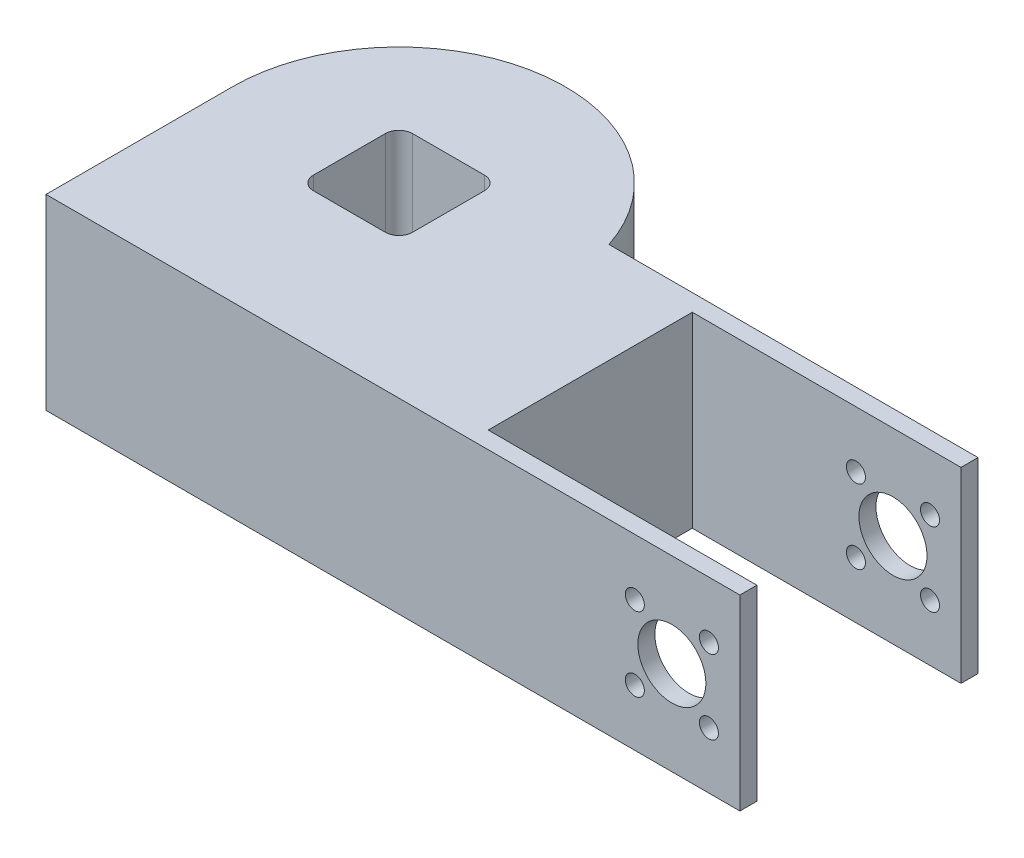
SolidWorks part; units mm, degrees
ref_plane "Front Plane" through (0, 0, 0) normal (0, 0, 1) x (1, 0, 0)
ref_plane "Top Plane" through (0, 0, 0) normal (0, 1, 0) x (1, 0, 0)
ref_plane "Right Plane" through (0, 0, 0) normal (1, 0, 0) x (0, 0, -1)
sketch "Sketch1" plane through (0, 0, 0) normal (0, 1, 0) x (1, 0, 0)
  circle A0 centre (0, 0) radius 31.0896
  dimension "D1" = 62.1792
extrude "Boss-Extrude1" add sketch "Sketch1" along normal blind 34.925
sketch "Sketch2" plane through (0, 34.925, 0) normal (0, 1, 0) x (1, 0, 0)
  line L0 (0, 0) -> (-31.0896, 0) construction
  line L1 (0, 0) -> (29.5534, 9.652) construction
  line L2 (-31.0896, 0) -> (-31.0896, -34.798)
  line L4 (45.1104, -34.798) -> (45.1104, 9.652)
  line L5 (-31.0896, -34.798) -> (45.1104, -34.798)
  line L7 (29.5534, 9.652) -> (45.1104, 9.652)
  circle A0 centre (0, 0) radius 31.0896 construction
  circle A2 centre (0, 0) radius 31.0896
  arc A3 (-31.0896, 0) -> (29.5534, 9.652) centre (0, 0) ccw
  dimension "D1" = 44.45
  dimension "D2" = 15.557
  dimension "D3" = 76.2
  dimension "D4" = 0
extrude "Boss-Extrude2" add sketch "Sketch2" against normal up to surface (34.925 mm away) up to face at (0, 0, 31.0896)
sketch "Sketch3" plane through (0, 34.925, 0) normal (0, 1, 0) x (1, 0, 0)
  line L0 (45.1104, -4.714) -> (45.1104, -34.798)
  line L2 (45.1104, -34.798) -> (98.4504, -34.798)
  line L3 (98.4504, -34.798) -> (98.4504, -31.623)
  line L4 (98.4504, -31.623) -> (48.2854, -31.623)
  line L5 (48.2854, -31.623) -> (48.2854, 6.477)
  line L6 (48.2854, 6.477) -> (98.4504, 6.477)
  line L7 (98.4504, 6.477) -> (98.4504, 9.652)
  line L8 (98.4504, 9.652) -> (45.1104, 9.652)
  line L9 (45.1104, -4.714) -> (45.1104, 9.652)
  dimension "D1" = 53.34
  dimension "D2" = 38.1
  dimension "D3" = 3.175
  dimension "D4" = 3.175
extrude "Boss-Extrude3" add sketch "Sketch3" against normal up to surface (34.925 mm away) up to face at (10.6953, 0, 4.883)
sketch "Sketch4" plane through (0, 0, -9.652) normal (0, 0, -1) x (-1, 0, 0)
  line L0 (-98.4504, 17.4625) -> (-85.7504, 17.4625) construction
  line L1 (-98.4504, 0) -> (-98.4504, 34.925) construction
  line L2 (-85.7504, 17.4625) -> (-92.6652, 10.5477) construction
  line L3 (-85.7504, 17.4625) -> (-92.6652, 24.3773) construction
  line L4 (-85.7504, 17.4625) -> (-92.6652, 10.5477) construction
  line L5 (-85.7504, 17.4625) -> (-78.8356, 10.5477) construction
  line L6 (-85.7504, 17.4625) -> (-78.8356, 24.3773) construction
  line L8 (-92.6652, 24.3773) -> (-98.4504, 24.3773) construction
  line L9 (-98.4504, 0) -> (-98.4504, 34.925) construction
  line L10 (-92.6652, 10.5477) -> (-98.4504, 10.5477) construction
  circle A0 centre (-85.7504, 17.4625) radius 6.35
  circle A1 centre (-78.8356, 10.5477) radius 1.778
  circle A3 centre (-92.6652, 24.3773) radius 1.778
  circle A4 centre (-92.6652, 10.5477) radius 1.778
  circle A5 centre (-78.8356, 24.3773) radius 1.778
  dimension "D1" = 12.7
  dimension "D2" = 12.7
  dimension "D3" = 3.556
  dimension "D5" = 19.558
  dimension "D4" = 19.558
extrude "Cut-Extrude1" cut sketch "Sketch4" against normal up to surface (44.45 mm away) up to face at (33.6804, 17.4625, 34.798)
sketch "Sketch5" plane through (0, 34.925, 0) normal (0, 1, 0) x (1, 0, 0)
  line L1 (-9.2497, 9.2497) -> (9.2497, 9.2497)
  line L2 (-9.2497, 9.2497) -> (-9.2497, -9.2497)
  line L3 (-9.2497, -9.2497) -> (9.2497, -9.2497)
  line L4 (9.2497, 9.2497) -> (9.2497, -9.2497)
  line L5 (-9.2497, 9.2497) -> (9.2497, -9.2497) construction
  line L6 (-9.2497, -9.2497) -> (9.2497, 9.2497) construction
  point P0 (0, 0)
  dimension "D1" = 26.162
extrude "Cut-Extrude2" cut sketch "Sketch5" against normal up to surface (34.925 mm away) up to face at (50.4031, 0, 8.3008)
fillet "Fillet3" radius 2.54 1 edges at (-9.2497, 17.4625, 9.2497)
fillet "Fillet4" radius 2.54 1 edges at (-9.2497, 17.4625, -9.2497)
fillet "Fillet5" radius 2.54 1 edges at (9.2497, 17.4625, -9.2497)
fillet "Fillet6" radius 2.54 1 edges at (9.2497, 17.4625, 9.2497)
